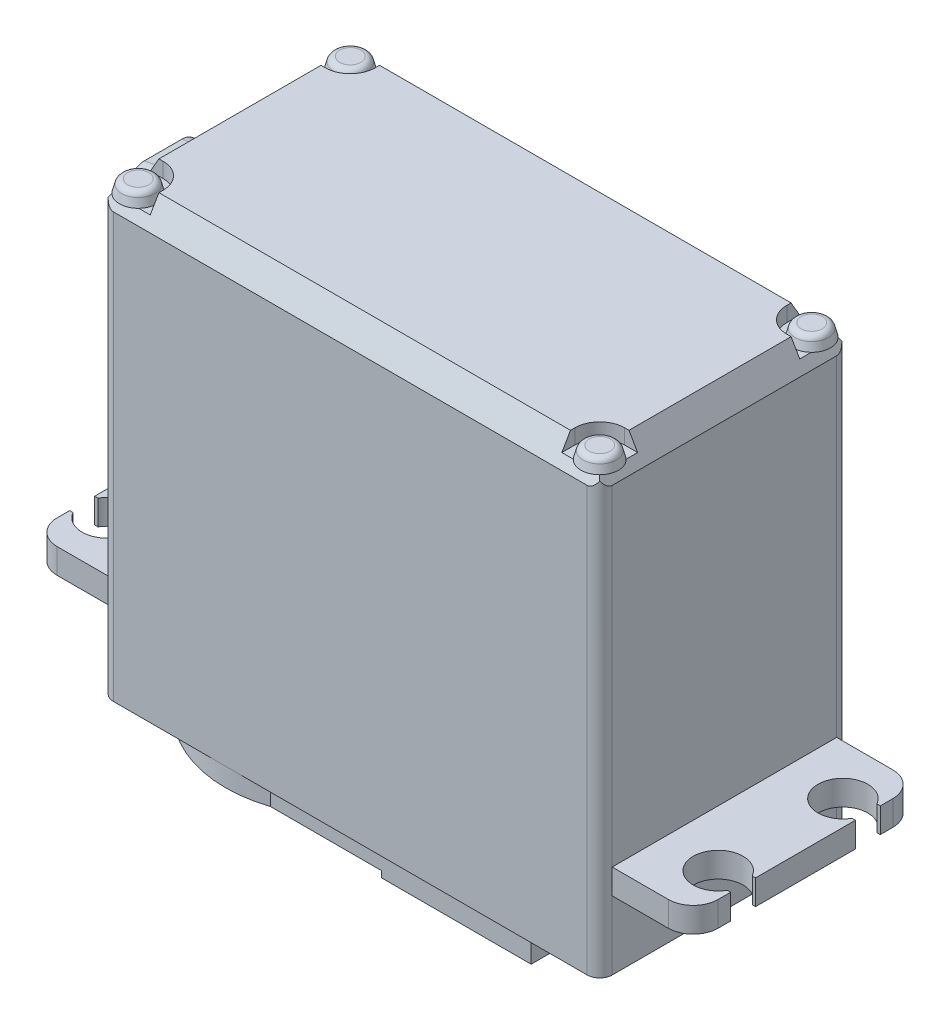
SolidWorks part; units mm, degrees
note: The reader was unsure of these and kept them because the rebuilt part matched: shared geometry of "草图1<2>".
ref_plane "前视基准面" through (0, 0, 0) normal (0, 0, 1) x (1, 0, 0)
ref_plane "上视基准面" through (0, 0, 0) normal (0, 1, 0) x (1, 0, 0)
ref_plane "右视基准面" through (0, 0, 0) normal (1, 0, 0) x (0, 0, -1)
sketch "草图1" plane through (0, 0, 0) normal (0, 1, 0) x (1, 0, 0)
  line L1 (0, 0) -> (40, 0)
  line L2 (0, 0) -> (0, -20)
  line L3 (0, -20) -> (40, -20)
  line L4 (40, 0) -> (40, -20)
  dimension "D1" = 40
  dimension "D2" = 20
extrude "凸台-拉伸1" add sketch "草图1" along normal blind 28.5
sketch "草图3" plane through (0, 0, 0) normal (0, 1, 0) x (1, 0, 0)
  line L0 (0, 0) -> (0, -20) construction
  line L7 (-6.5, -1) -> (46.5, -1)
  line L8 (-6.5, -1) -> (-6.5, -19)
  line L9 (-6.5, -19) -> (46.5, -19)
  line L10 (46.5, -1) -> (46.5, -19)
  line L11 (-6.5, -10) -> (0, -10) construction
  line L12 (20, -1) -> (20, 0) construction
  line L13 (40, 0) -> (0, 0) construction
  line L14 (40, 0) -> (0, 0) construction
  dimension "D1" = 18
  dimension "D2" = 53
sketch "草图8" plane through (0, 0, 0) normal (0, 1, 0) x (1, 0, 0)
  line L0 (0, -10) -> (-4.5, -10) construction
  line L1 (0, 0) -> (0, -20) construction
  line L2 (0, -10) -> (40, -10) construction
  line L3 (40, -20) -> (40, 0) construction
  line L4 (40, -10) -> (44.5, -10) construction
  line L5 (44.5, -10) -> (44.5, -5) construction
  line L6 (44.5, -10) -> (44.5, -15) construction
  line L7 (-4.5, -10) -> (-4.5, -5) construction
  line L8 (-4.5, -10) -> (-4.5, -15) construction
  line L9 (-4.5, -5) -> (-9.5, -5) construction
  line L10 (-4.5, -15) -> (-9.5, -15) construction
  line L11 (-9.5, -5) -> (-9.5, -4) construction
  line L12 (-9.5, -5) -> (-9.5, -6) construction
  line L13 (-9.5, -15) -> (-9.5, -14) construction
  line L14 (-9.5, -15) -> (-9.5, -16) construction
  line L15 (44.5, -5) -> (49.5, -5) construction
  line L16 (49.5, -5) -> (49.5, -4) construction
  line L17 (49.5, -5) -> (49.5, -6) construction
  line L18 (44.5, -15) -> (49.5, -15) construction
  line L19 (49.5, -15) -> (49.5, -14) construction
  line L20 (49.5, -15) -> (49.5, -16) construction
  line L21 (-9.5, -6) -> (-6.2321, -6)
  line L22 (-9.5, -4) -> (-6.2321, -4)
  line L23 (-9.5, -14) -> (-6.2321, -14)
  line L24 (-9.5, -16) -> (-6.2321, -16)
  line L25 (49.5, -4) -> (46.2321, -4)
  line L26 (49.5, -6) -> (46.2321, -6)
  line L27 (49.5, -14) -> (46.2321, -14)
  line L28 (49.5, -16) -> (46.2321, -16)
  line L29 (49.5, -4) -> (49.5, -6)
  line L30 (49.5, -14) -> (49.5, -16)
  line L31 (-9.5, -4) -> (-9.5, -6)
  line L32 (-9.5, -14) -> (-9.5, -16)
  circle A0 centre (-4.5, -5) radius 2 construction
  circle A1 centre (-4.5, -15) radius 2 construction
  circle A2 centre (44.5, -5) radius 2 construction
  circle A3 centre (44.5, -15) radius 2 construction
  arc A4 (-6.2321, -4) -> (-6.2352, -5.9945) centre (-4.5, -5) cw
  arc A5 (-6.2321, -14) -> (-6.2598, -15.9504) centre (-4.5, -15) cw
  arc A6 (46.2321, -4) -> (46.2321, -6) centre (44.5, -5) ccw
  arc A7 (46.2321, -14) -> (46.2321, -16) centre (44.5, -15) ccw
  dimension "D2" = 4
  dimension "D3" = 4
  dimension "D4" = 4
  dimension "D5" = 4
  dimension "D1" = 49
  dimension "D6" = 10
  dimension "D7" = 10
  dimension "D8" = 1
  dimension "D9" = 1
  dimension "D10" = 1
  dimension "D11" = 1
  dimension "D12" = 1
  dimension "D13" = 1
  dimension "D14" = 1
  dimension "D15" = 1
  dimension "D16" = 5
  dimension "D17" = 5
  dimension "D18" = 5
  dimension "D19" = 5
sketch "草图7" plane through (0, 0, 0) normal (0, 1, 0) x (1, 0, 0)
  line L0 (0, -10) -> (10, -10)
  line L1 (0, 0) -> (0, -20) construction
  circle A0 centre (10, -10) radius 2.5
  dimension "D2" = 5
  dimension "D1" = 10
extrude "凸台-拉伸4" add sketch "草图7" against normal blind 6.9754 contours A0
extrude "凸台-拉伸5" add sketch "草图1<2>" against normal blind 7.5
sketch "草图1<2>" plane through (0, 0, 0) normal (0, 1, 0) x (1, 0, 0) same geometry as "草图1"
extrude "凸台-拉伸6" add sketch "草图3" against normal blind 2
extrude "切除-拉伸4" cut sketch "草图8" against normal mid plane 10
sketch "草图9" plane through (0, -7.5, 0) normal (0, -1, 0) x (1, 0, 0)
  line L0 (40, 10) -> (34, 10) construction
  line L1 (40, 20) -> (40, 0) construction
  line L2 (34, 19.5) -> (34, 0.5)
  line L3 (0, 20) -> (40, 20) construction
  line L4 (40, 0) -> (0, 0) construction
  line L5 (34, 19.5) -> (13.1225, 19.5)
  line L6 (34, 0.5) -> (13.1225, 0.5)
  line L7 (0, 0) -> (0, 20) construction
  circle A0 centre (10, 10) radius 10 construction
  arc A1 (13.1225, 19.5) -> (13.1225, 0.5) centre (10, 10) ccw
  dimension "D6" = 20
  dimension "D1" = 6
  dimension "D2" = 20
  dimension "D3" = 19
  dimension "D4" = 10
  dimension "D5" = 10
extrude "凸台-拉伸7" add sketch "草图9" along normal blind 1.5
sketch "草图13" plane through (0, -7.5, 0) normal (0, -1, 0) x (1, 0, 0)
  line L0 (34, 0.5) -> (13.1225, 0.5) construction
  line L1 (34, 19.5) -> (22, 19.5)
  line L2 (34, 19.5) -> (34, 0.5)
  line L3 (34, 0.5) -> (22, 0.5)
  line L4 (22, 19.5) -> (22, 0.5)
  dimension "D1" = 12
extrude "凸台-拉伸8" add sketch "草图13" along normal blind 2
sketch "草图14" plane through (0, -7.5, 0) normal (0, -1, 0) x (1, 0, 0)
  line L0 (40, 19) -> (40, 1) construction
  line L1 (31, 10) -> (40, 10) construction
  line L2 (40, 20) -> (40, 0) construction
  circle A0 centre (31, 10) radius 6
  dimension "D2" = 12
  dimension "D1" = 9
extrude "凸台-拉伸9" add sketch "草图14" along normal blind 1.5 contours A0
ref_plane "基准面2" through (0, 0, 10) normal (0, 0, -1) x (-1, 0, 0)
sketch "草图15" plane through (0, 0, 10) normal (0, 0, -1) x (-1, 0, 0)
  line L1 (0, 28.5) -> (0, -7.5) construction
  line L2 (0, -3.2) -> (-40, -3.2)
  line L3 (-40, 28.5) -> (-40, -7.5) construction
  line L5 (-40, -3.2) -> (-46.5, -2)
  line L6 (-46.5, -2) -> (6.5, -2)
  line L7 (6.5, -2) -> (0, -3.2)
  dimension "D1" = 1.2
extrude "凸台-拉伸10" add sketch "草图15" along normal mid plane 0.5
sketch "草图16" plane through (0, 0, 0) normal (0, 0, 1) x (1, 0, 0)
  line L0 (0, 26.5) -> (1.1547, 28.5)
  line L1 (0, 28.5) -> (0, -7.5) construction
  line L2 (0, 28.5) -> (40, 28.5) construction
  line L3 (1.1547, 28.5) -> (38.8453, 28.5)
  line L4 (38.8453, 28.5) -> (40, 26.5)
  line L5 (40, 28.5) -> (40, -7.5) construction
  line L6 (40, 26.5) -> (45, 26.5)
  line L7 (45, 26.5) -> (45, 36.5)
  line L8 (45, 36.5) -> (-5, 36.5)
  line L9 (-5, 36.5) -> (-5, 26.5)
  line L10 (-5, 26.5) -> (0, 26.5)
  dimension "D1" = 10
  dimension "D2" = 50
  dimension "D3" = 120
  dimension "D4" = 2
  dimension "D5" = 2
  dimension "D6" = 120
extrude "切除-拉伸5" cut sketch "草图16" against normal mid plane 100 contours L9 L10 L0 L3 L4 L6 L7 L8
sketch "草图18" plane through (0, 0, 0) normal (1, 0, 0) x (0, 0, -1)
  line L0 (-20, 26.5) -> (-18.8453, 28.5)
  line L1 (0, 28.5) -> (-20, 28.5) construction
  line L2 (-18.8453, 28.5) -> (-1.1547, 28.5)
  line L3 (-1.1547, 28.5) -> (0, 26.5)
  line L4 (0, 26.5) -> (15, 26.5)
  line L5 (15, 26.5) -> (15, 36.5)
  line L6 (15, 36.5) -> (-35, 36.5)
  line L7 (-35, 36.5) -> (-35, 26.5)
  line L8 (-35, 26.5) -> (-20, 26.5)
  dimension "D1" = 120
  dimension "D2" = 120
  dimension "D3" = 50
  dimension "D4" = 10
extrude "切除-拉伸6" cut sketch "草图18" against normal mid plane 100 contours L6 L7 L8 L0 L2 L3 L4 L5
sketch "草图22" plane through (0, 28.5, 0) normal (0, 1, 0) x (1, 0, 0)
  line L0 (0, 0) -> (0, -1.5)
  line L1 (0, -1) -> (0, -19) construction
  line L2 (0, -1.5) -> (1.5, -1.5)
  line L3 (3.5, -1.5) -> (3.5, 0.5)
  line L4 (3.5, 0.5) -> (-0.5, 0.5)
  line L5 (1.5, -3.5) -> (-0.5, -3.5)
  line L6 (-0.5, -3.5) -> (-0.5, 0.5)
  line L7 (19.8, -10) -> (-19.8, -10) construction
  line L8 (3.5, -18.5) -> (3.5, -20.5)
  line L9 (1.5, -16.5) -> (-0.5, -16.5)
  line L10 (-0.5, -16.5) -> (-0.5, -20.5)
  line L11 (3.5, -20.5) -> (-0.5, -20.5)
  line L12 (20, -1.1547) -> (20, -18.8453) construction
  line L13 (1.1547, -1.1547) -> (38.8453, -1.1547) construction
  line L14 (1.1547, -18.8453) -> (38.8453, -18.8453) construction
  line L15 (36.5, -18.5) -> (36.5, -20.5)
  line L16 (36.5, -20.5) -> (40.5, -20.5)
  line L17 (40.5, -16.5) -> (40.5, -20.5)
  line L18 (38.5, -16.5) -> (40.5, -16.5)
  line L19 (36.5, -1.5) -> (36.5, 0.5)
  line L20 (38.5, -3.5) -> (40.5, -3.5)
  line L21 (40.5, -3.5) -> (40.5, 0.5)
  line L22 (36.5, 0.5) -> (40.5, 0.5)
  circle A0 centre (1.5, -1.5) radius 2 construction
  arc A1 (3.5, -1.5) -> (1.3994, -3.4975) centre (1.5, -1.5) cw
  arc A2 (3.5, -18.5) -> (1.3994, -16.5025) centre (1.5, -18.5) ccw
  arc A3 (36.5, -18.5) -> (38.6006, -16.5025) centre (38.5, -18.5) cw
  arc A4 (36.5, -1.5) -> (38.6006, -3.4975) centre (38.5, -1.5) ccw
  point P13 (0.5, -3.5)
  point P20 (0.5, -16.5)
  dimension "D3" = 4
  dimension "D1" = 1.5
  dimension "D2" = 1.5
  dimension "D4" = 4
extrude "切除-拉伸11" cut sketch "草图22" against normal blind 1.2
sketch "草图24" plane through (0, 28.5, 0) normal (0, 1, 0) x (1, 0, 0)
  line L0 (0, 0) -> (1.5, 0)
  line L1 (0, 0) -> (40, 0) construction
  line L2 (1.5, 0) -> (1.5, -1.5)
  line L3 (40, 0) -> (38.5, 0)
  line L4 (38.5, 0) -> (38.5, -1.5)
  line L5 (40, -20) -> (38.5, -20)
  line L6 (0, -20) -> (40, -20) construction
  line L7 (38.5, -20) -> (38.5, -18.5)
  line L8 (0, -20) -> (1.5, -20)
  line L9 (1.5, -20) -> (1.5, -18.5)
  circle A0 centre (1.5, -1.5) radius 1.5
  circle A1 centre (38.5, -1.5) radius 1.5
  circle A2 centre (38.5, -18.5) radius 1.5
  circle A3 centre (1.5, -18.5) radius 1.5
  dimension "D1" = 1.5
  dimension "D2" = 1.5
  dimension "D3" = 1.5
  dimension "D4" = 1.5
  dimension "D5" = 1.5
  dimension "D6" = 1.5
  dimension "D7" = 1.5
  dimension "D8" = 1.5
sketch "草图25" plane through (0, 27.3, 0) normal (0, 1, 0) x (1, 0, 0)
  circle A0 centre (1.5, -1.5) radius 1.5
  circle A1 centre (38.5, -1.5) radius 1.5
  circle A2 centre (38.5, -18.5) radius 1.5
  circle A3 centre (1.5, -18.5) radius 1.5
extrude "凸台-拉伸12" add sketch "草图25" along normal blind 1 draft 15
sketch "草图29" plane through (0, -9, 0) normal (0, -1, 0) x (1, 0, 0)
  circle A0 centre (10, 10) radius 6.25
  dimension "D1" = 12.5
extrude "凸台-拉伸15" add sketch "草图29" along normal blind 1.2
sketch "草图30" plane through (0, -10.2, 0) normal (0, -1, 0) x (1, 0, 0)
  circle A0 centre (10, 10) radius 5
  dimension "D1" = 10
extrude "凸台-拉伸16" add sketch "草图30" along normal blind 0.3
sketch "草图31" plane through (0, -10.5, 0) normal (0, -1, 0) x (1, 0, 0)
  line L0 (10, 10) -> (13, 10) construction
  line L1 (10, 10) -> (12.9763, 10.376) construction
  line L2 (10, 10) -> (12.9057, 10.7461) construction
  line L3 (12.9763, 10.376) -> (12.4215, 10.6217)
  line L4 (12.9763, 10.376) -> (12.5, 10)
  line L5 (12.9763, 9.624) -> (12.5, 10)
  line L6 (12.9763, 9.624) -> (12.4215, 9.3783)
  line L7 (12.7893, 8.8956) -> (12.4215, 9.3783)
  line L8 (12.7893, 8.8956) -> (12.1908, 8.7956)
  line L9 (12.4271, 8.2366) -> (12.1908, 8.7956)
  line L10 (12.4271, 8.2366) -> (11.8224, 8.2886)
  line L11 (11.9123, 7.6885) -> (11.8224, 8.2886)
  line L12 (11.9123, 7.6885) -> (11.3396, 7.8892)
  line L13 (11.2773, 7.2855) -> (11.3396, 7.8892)
  line L14 (11.2773, 7.2855) -> (10.7725, 7.6224)
  line L15 (10.5621, 7.0531) -> (10.7725, 7.6224)
  line L16 (10.5621, 7.0531) -> (10.157, 7.5049)
  line L17 (9.8116, 7.0059) -> (10.157, 7.5049)
  line L18 (9.8116, 7.0059) -> (9.5315, 7.5443)
  line L19 (9.0729, 7.1468) -> (9.5315, 7.5443)
  line L20 (9.0729, 7.1468) -> (8.9356, 7.7379)
  line L21 (8.3925, 7.467) -> (8.9356, 7.7379)
  line L22 (8.3925, 7.467) -> (8.4064, 8.0737)
  line L23 (7.8131, 7.9464) -> (8.4064, 8.0737)
  line L24 (7.8131, 7.9464) -> (7.9775, 8.5305)
  line L25 (7.3711, 8.5547) -> (7.9775, 8.5305)
  line L26 (7.3711, 8.5547) -> (7.6756, 9.0797)
  line L27 (7.0943, 9.2539) -> (7.6756, 9.0797)
  line L28 (7.0943, 9.2539) -> (7.5197, 9.6867)
  line L29 (7, 10) -> (7.5197, 9.6867)
  line L30 (7, 10) -> (7.5197, 10.3133)
  line L31 (7.0943, 10.7461) -> (7.5197, 10.3133)
  line L32 (7.0943, 10.7461) -> (7.6756, 10.9203)
  line L33 (7.3711, 11.4453) -> (7.6756, 10.9203)
  line L34 (7.3711, 11.4453) -> (7.9775, 11.4695)
  line L35 (7.8131, 12.0536) -> (7.9775, 11.4695)
  line L36 (7.8131, 12.0536) -> (8.4064, 11.9263)
  line L37 (8.3925, 12.533) -> (8.4064, 11.9263)
  line L38 (8.3925, 12.533) -> (8.9356, 12.2621)
  line L39 (9.0729, 12.8532) -> (8.9356, 12.2621)
  line L40 (9.0729, 12.8532) -> (9.5315, 12.4557)
  line L41 (9.8116, 12.9941) -> (9.5315, 12.4557)
  line L42 (9.8116, 12.9941) -> (10.157, 12.4951)
  line L43 (10.5621, 12.9469) -> (10.157, 12.4951)
  line L44 (10.5621, 12.9469) -> (10.7725, 12.3776)
  line L45 (11.2773, 12.7145) -> (10.7725, 12.3776)
  line L46 (11.2773, 12.7145) -> (11.3396, 12.1108)
  line L47 (11.9123, 12.3115) -> (11.3396, 12.1108)
  line L48 (11.9123, 12.3115) -> (11.8224, 11.7114)
  line L49 (12.4271, 11.7634) -> (11.8224, 11.7114)
  line L50 (12.4271, 11.7634) -> (12.1908, 11.2044)
  line L51 (12.7893, 11.1044) -> (12.1908, 11.2044)
  line L52 (12.7893, 11.1044) -> (12.4215, 10.6217)
  circle A0 centre (10, 10) radius 3 construction
  circle A1 centre (10, 10) radius 2.5 construction
  point P83 (10, 10)
  dimension "D1" = 5
  dimension "D2" = 6
  dimension "D5" = 0.5
  dimension "D3" = 7.2
  dimension "D4" = 7.2
  dimension "D6" = 25
extrude "凸台-拉伸17" add sketch "草图31" along normal blind 3.5
sketch "草图33" plane through (0, -10.5, 0) normal (0, -1, 0) x (1, 0, 0)
  circle A0 centre (10, 10) radius 1.25
  dimension "D1" = 2.5
extrude "切除-拉伸12" cut sketch "草图33" along normal blind 10 contours A0
fillet "圆角1" radius 2 4 edges at (46.5, -1, 19) (46.5, -1, 1) (-6.5, -1, 1) (-6.5, -1, 19)
fillet "圆角2" radius 1 4 edges at (0, 9.5, 20) (40, 9.5, 20) (40, 9.5, 0) (0, 9.5, 0)
fillet "圆角4" radius 0.5 4 edges at (38.5, 28.3, 2.7321) (1.5, 28.3, 2.7321) (1.5, 28.3, 19.7321) (38.5, 28.3, 19.7321)
sketch "草图34" plane through (0, 0, 0) normal (-1, 0, 0) x (0, 0, 1)
  line L0 (10, 28.5) -> (10, 21.5) construction
  line L1 (16.5, 28.5) -> (3.5, 28.5) construction
  line L2 (10, 18.7) -> (10, -18.7) construction
  line L3 (10, 21.5) -> (6.5, 21.5) construction
  line L4 (6.5, 23.75) -> (13.5, 23.75)
  line L5 (6.5, 23.75) -> (6.5, 19.25)
  line L6 (6.5, 19.25) -> (13.5, 19.25)
  line L7 (13.5, 23.75) -> (13.5, 19.25)
  point P12 (10, 23.75)
  dimension "D1" = 7
  dimension "D2" = 7
  dimension "D3" = 4.5
extrude "凸台-拉伸18" add sketch "草图34" along normal blind 1 contours L4 L7 L6 L5
sketch "草图35" plane through (-1, 0, 0) normal (-1, 0, 0) x (0, 0, 1)
  line L0 (10, 23.5) -> (10, 21.5) construction
  line L1 (10, 18.7) -> (10, -18.7) construction
  line L2 (10, 21.5) -> (10, 19.5) construction
  line L3 (10, 21.5) -> (13.5, 21.5) construction
  line L4 (13.5, 23.75) -> (13.5, 19.25) construction
  line L5 (8.5, 23.5) -> (11.5, 23.5)
  line L6 (8.5, 19.5) -> (11.5, 19.5)
  circle A0 centre (11.5, 21.5) radius 2 construction
  arc A1 (11.5, 23.5) -> (11.5, 19.5) centre (11.5, 21.5) cw
  arc A2 (8.5, 23.5) -> (8.5, 19.5) centre (8.5, 21.5) ccw
  dimension "D4" = 3.5
  dimension "D1" = 2
  dimension "D2" = 2
  dimension "D3" = 1.5
extrude "凸台-拉伸19" add sketch "草图35" along normal blind 4 draft 10 contours L5 A1 L6 A2
